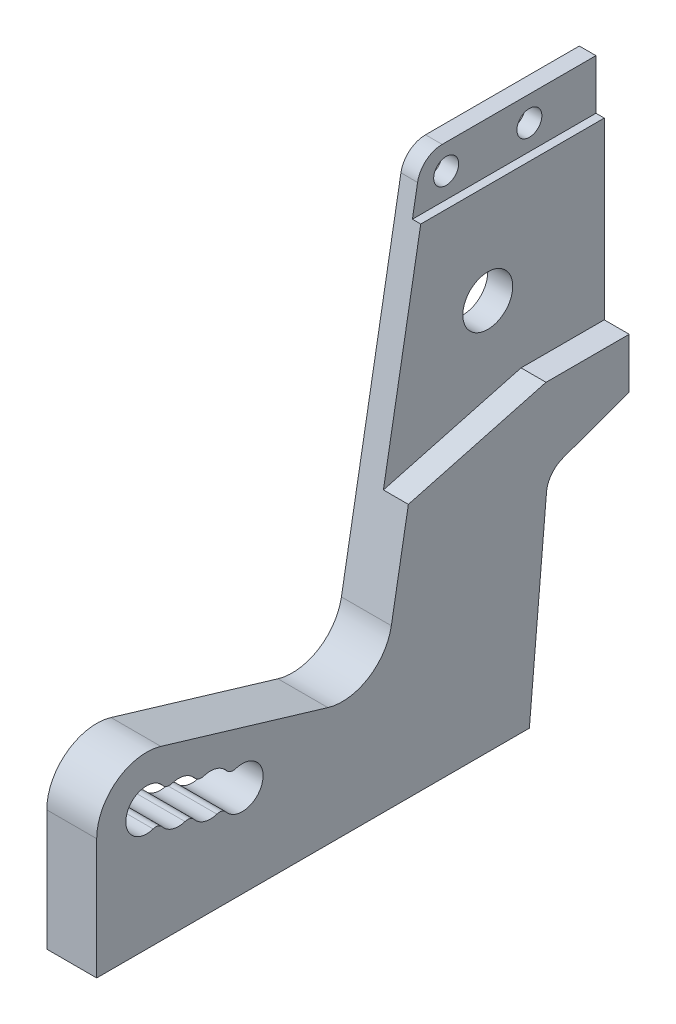
SolidWorks part; units mm, degrees
material "1060 Alloy"
ref_plane "Front Plane" through (0, 0, 0) normal (0, 0, 1) x (1, 0, 0)
ref_plane "Top Plane" through (0, 0, 0) normal (0, 1, 0) x (1, 0, 0)
ref_plane "Right Plane" through (0, 0, 0) normal (1, 0, 0) x (0, 0, -1)
sketch "Sketch1" plane through (0, 0, 0) normal (1, 0, 0) x (0, 0, -1)
  line L1 (0, 0) -> (64, 0)
  line L2 (0, 0) -> (0, 62)
  line L3 (0, 62) -> (64, 62)
  line L4 (64, 0) -> (64, 62)
  circle A0 centre (6, 14.5) radius 2.5
  circle A1 centre (50, 44) radius 3
  dimension "D1" = 6
  dimension "D2" = 5
  dimension "D3" = 14.5
  dimension "D4" = 6
  dimension "D5" = 44
  dimension "D6" = 50
  dimension "D7" = 64
  dimension "D8" = 62
extrude "Boss-Extrude1" add sketch "Sketch1" along normal blind 6
sketch "Sketch3" plane through (6, 0, 0) normal (1, 0, 0) x (0, 0, -1)
  line L57 (64, 0) -> (52, 0)
  line L58 (64, 0) -> (64, 29)
  line L59 (64, 29) -> (54.2259, 25.4425)
  line L60 (52, 0) -> (54.2259, 25.4425)
  dimension "D1" = 70
  dimension "D2" = 29
  dimension "D3" = 52
  dimension "D4" = 85
extrude "Cut-Extrude2" cut sketch "Sketch3" against normal up to next
fillet "Fillet2" radius 3 1 edges at (3, 25.4425, -54.2259)
hole_wizard "Tap Drill for M3 Tap1" positions "Sketch5" profile "Sketch4" hole size "M3" standard "ISO"
sketch "Sketch5" plane through (0, 0, 0) normal (0, -1, 0) x (-1, 0, 0)
  line L0 (0, 0) -> (0, 52) construction
  line L1 (-6, 0) -> (0, 0) construction
  point P0 (-3, 48)
  point P2 (-3, 12)
  dimension "D1" = 3
  dimension "D2" = 12
  dimension "D3" = 36
sketch "Sketch4" plane through (3, 0, -48) normal (1, 0, 0) x (0, 0, -1)
  line L0 (0, 0) -> (0, 9.7511)
  line L1 (0, 9.7511) -> (1.25, 9)
  line L2 (1.25, 9) -> (1.25, 0)
  line L5 (1.25, 0) -> (0, 0)
  line L10 (0, 9.7511) -> (-1.25, 9) construction
  line L11 (0, -6.35) -> (0, 107.95) construction
  dimension "Hole Dia." = 2.5
  dimension "Hole Depth" = 9
  dimension "Drill Angle" = 118
sketch "Sketch9" plane through (6, 0, 0) normal (1, 0, 0) x (0, 0, -1)
  line L0 (7.7183, 20.2487) -> (27.7834, 14.2513)
  line L1 (0, 0) -> (52, 0) construction
  line L19 (43, 62) -> (35.4106, 18.9581)
  line L21 (0, 62) -> (0, 0) construction
  line L22 (43, 62) -> (0, 62)
  line L23 (0, 62) -> (0, 14.5)
  line L24 (0, 62) -> (0, 0) construction
  line L25 (64, 62) -> (0, 62) construction
  arc A0 (35.4106, 18.9581) -> (27.7834, 14.2513) centre (29.5017, 20) cw
  arc A12 (0, 14.5) -> (7.7183, 20.2487) centre (6, 14.5) cw
  circle A16 centre (6, 14.5) radius 2.5 construction
  dimension "D1" = 43
  dimension "D2" = 80
  dimension "D3" = 20
extrude "Cut-Extrude3" cut sketch "Sketch9" against normal blind 8
sketch "Sketch13" plane through (6, 0, 0) normal (1, 0, 0) x (0, 0, -1)
  line L0 (64, 29) -> (64, 62) construction
  line L1 (54, 35) -> (64, 35)
  line L2 (64, 62) -> (43, 62) construction
  line L3 (64, 62) -> (43, 62)
  line L4 (64, 35) -> (64, 62)
  line L5 (35.4106, 18.9581) -> (43, 62) construction
  line L11 (43, 62) -> (37.4576, 30.5675)
  line L15 (37.4576, 30.5675) -> (54, 35)
  dimension "D1" = 10
  dimension "D2" = 65
  dimension "D3" = 27
extrude "Cut-Extrude4" cut sketch "Sketch13" against normal blind 3
fillet "Fillet3" radius 3 1 edges at (1.5, 62, -43)
sketch "Sketch14" plane through (3, 0, 0) normal (1, 0, 0) x (0, 0, -1)
  line L0 (64, 35) -> (64, 62) construction
  line L1 (64, 62) -> (45.5173, 62) construction
  circle A0 centre (56, 59) radius 1.5
  circle A1 centre (46, 59) radius 1.5
  dimension "D1" = 3
  dimension "D2" = 10
  dimension "D3" = 8
  dimension "D4" = 3
extrude "Cut-Extrude5" cut sketch "Sketch14" against normal up to next
sketch "Sketch15" plane through (0, 0, 0) normal (-1, 0, 0) x (0, 0, 1)
  line L0 (-6, 14.5) -> (-26.0652, 8.5026) construction
  line L1 (-27.7834, 14.2513) -> (-7.7183, 20.2487) construction
  circle A0 centre (-9.8325, 13.3545) radius 2.5
  circle A1 centre (-6, 14.5) radius 2.5 construction
  dimension "D1" = 4
extrude "Cut-Extrude6" cut sketch "Sketch15" against normal up to next
pattern_linear "LPattern3" count 3 spacing 4 along (0, -0.2864, -0.9581) of "Cut-Extrude6"
fillet "Fillet4" radius 1 6 edges at (3, 12.4901, -7.4867) (3, 11.3446, -11.3191) (3, 10.1991, -15.1516) (3, 13.0734, -16.0107) (3, 14.2189, -12.1783) (3, 15.3644, -8.3458)
sketch "Sketch16" plane through (3, 0, 0) normal (1, 0, 0) x (0, 0, -1)
  line L0 (42.5629, 59.5209) -> (37.4576, 30.5675) construction
  line L1 (64, 62) -> (41.942, 62)
  line L2 (64, 62) -> (64, 56)
  line L3 (64, 56) -> (41.942, 56)
  line L4 (41.942, 62) -> (41.942, 56)
  dimension "D1" = 6
extrude "Cut-Extrude7" cut sketch "Sketch16" against normal blind 1
